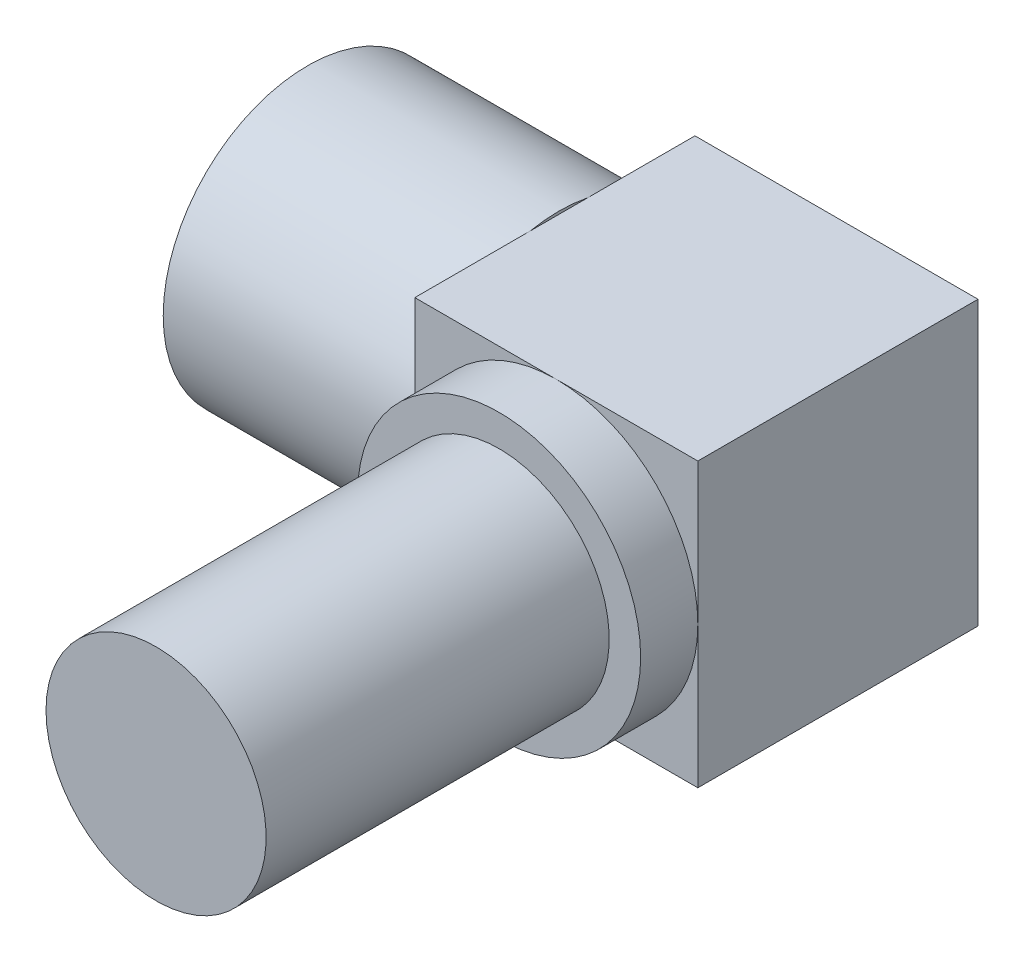
SolidWorks part; units mm, degrees
ref_plane "Front" through (0, 0, 0) normal (0, 0, 1) x (1, 0, 0)
ref_plane "Top" through (0, 0, 0) normal (0, 1, 0) x (1, 0, 0)
ref_plane "Right" through (0, 0, 0) normal (1, 0, 0) x (0, 0, -1)
sketch "Sketch1" plane through (0, 0, 0) normal (0, 0, 1) x (1, 0, 0)
  line L1 (-27.9811, 12.3265) -> (-2.8351, 12.3265)
  line L2 (-27.9811, 12.3265) -> (-27.9811, -12.8195)
  line L3 (-27.9811, -12.8195) -> (-2.8351, -12.8195)
  line L4 (-2.8351, 12.3265) -> (-2.8351, -12.8195)
  dimension "D1" = 25.146
  dimension "D2" = 25.146
extrude "Boss-Extrude1" add sketch "Sketch1" along normal blind 24.892
sketch "Sketch2" plane through (0, 0, 24.892) normal (0, 0, 1) x (1, 0, 0)
  line L0 (-15.4081, 12.3265) -> (-15.4081, -12.8195)
  line L1 (-27.9811, -0.2465) -> (-2.8351, -0.2465)
  line L4 (-27.9811, 12.3265) -> (-27.9811, -12.8195)
  line L5 (-27.9811, -12.8195) -> (-2.8351, -12.8195)
  line L6 (-2.8351, -12.8195) -> (-2.8351, 12.3265)
  line L7 (-2.8351, 12.3265) -> (-27.9811, 12.3265)
  line L8 (-27.9811, 12.3265) -> (-27.9811, -12.8195)
  line L9 (-27.9811, -12.8195) -> (-2.8351, -12.8195)
  line L10 (-2.8351, -12.8195) -> (-2.8351, 12.3265)
  line L11 (-2.8351, 12.3265) -> (-27.9811, 12.3265)
  circle A0 centre (-15.4081, -0.2465) radius 12.573
  dimension "D1" = 0
extrude "Boss-Extrude2" add sketch "Sketch2" along normal blind 5.08 contours L0 A0 L1 | L1 A0 L0 | L0 A0 L1 | L1 A0 L0 region at (-10.0719, 5.0896, 24.892) region at (-20.7442, 5.0896, 24.892) region at (-10.0719, -5.5827, 24.892) region at (-20.7442, -5.5827, 24.892)
sketch "Sketch3" plane through (0, 0, 29.972) normal (0, 0, 1) x (1, 0, 0)
  circle A0 centre (-15.4081, -0.2465) radius 9.779
  circle A1 centre (-15.4081, -0.2465) radius 12.573
  circle A2 centre (-15.4081, -0.2465) radius 12.573
  dimension "D1" = 0
extrude "Boss-Extrude3" add sketch "Sketch3" along normal blind 30.48 contours A0 region at (-15.4081, -0.2465, 29.972)
sketch "Sketch4" plane through (-27.9811, 0, 0) normal (-1, 0, 0) x (0, 0, 1)
  line L0 (24.892, -0.2465) -> (0, -0.2465)
  line L5 (0, 12.3265) -> (0, -12.8195)
  line L6 (0, -12.8195) -> (24.892, -12.8195)
  line L7 (24.892, -12.8195) -> (24.892, -0.2465)
  line L8 (24.892, -0.2465) -> (24.892, 12.3265)
  line L9 (24.892, 12.3265) -> (0, 12.3265)
  line L10 (0, 12.3265) -> (0, -12.8195)
  line L11 (0, -12.8195) -> (24.892, -12.8195)
  line L12 (24.892, -12.8195) -> (24.892, -0.2465)
  line L13 (24.892, -0.2465) -> (24.892, 12.3265)
  line L14 (24.892, 12.3265) -> (0, 12.3265)
  circle A0 centre (12.065, -0.2465) radius 12.827
  dimension "D2" = 25.654
  dimension "D1" = 0
extrude "Boss-Extrude4" add sketch "Sketch4" along normal blind 22.352 contours L0 A0 L14 L10 | L14 A0 | L0 A0 L11 | L10 A0 L0 | L11 A0 region at (-27.9811, -5.6992, 12.1728) region at (-27.9811, 5.2062, 12.1728) region at (-27.9811, -0.2465, -0.3056) region at (-27.9811, 12.4282, 12.065) region at (-27.9811, -12.9212, 12.065)
